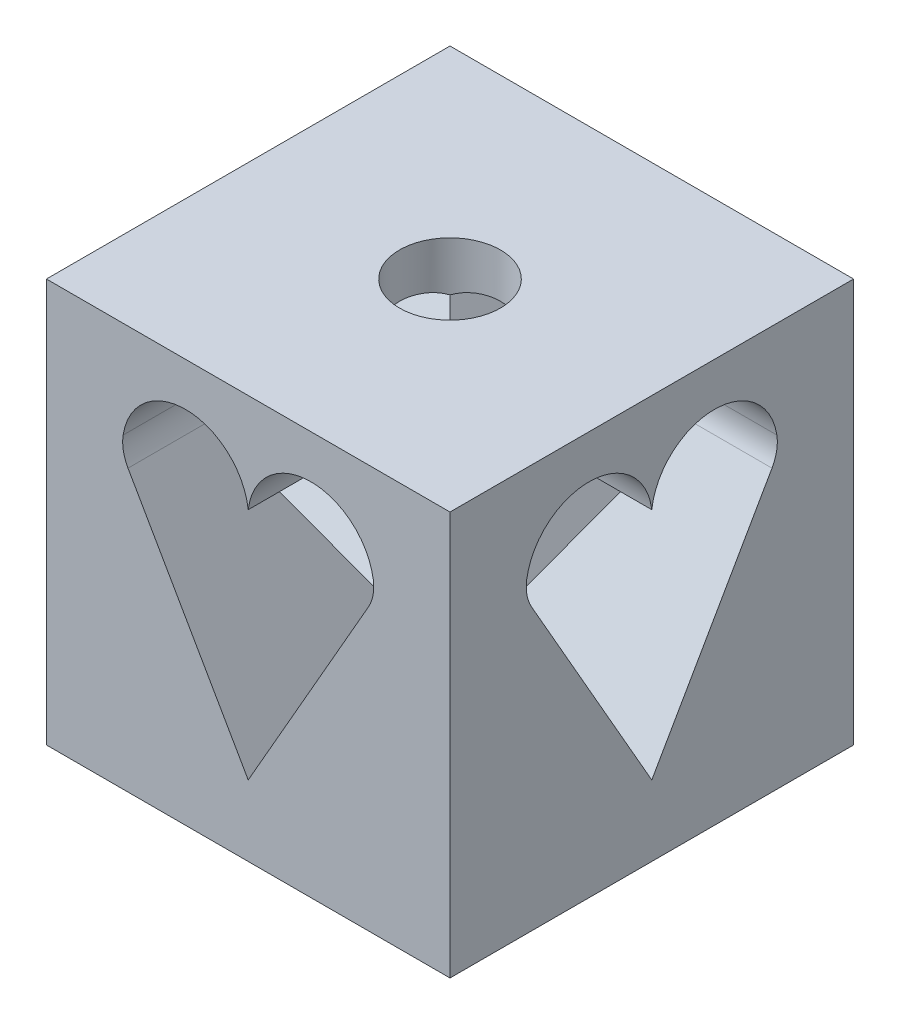
SolidWorks part; units mm, degrees
ref_plane "Front Plane" through (0, 0, 0) normal (0, 0, 1) x (1, 0, 0)
ref_plane "Top Plane" through (0, 0, 0) normal (0, 1, 0) x (1, 0, 0)
ref_plane "Right Plane" through (0, 0, 0) normal (1, 0, 0) x (0, 0, -1)
sketch "Sketch1" plane through (0, 0, 0) normal (0, 1, 0) x (1, 0, 0)
  line L1 (50, 50) -> (-50, 50)
  line L2 (50, 50) -> (50, -50)
  line L3 (50, -50) -> (-50, -50)
  line L4 (-50, 50) -> (-50, -50)
  line L5 (50, 50) -> (-50, -50) construction
  line L6 (50, -50) -> (-50, 50) construction
  point P0 (0, 0)
  dimension "D1" = 100
  dimension "D2" = 100
extrude "Boss-Extrude1" add sketch "Sketch1" along normal blind 100
ref_axis "Axis1" through (0, 105, 0) along (0, -1, 0)
sketch "Sketch2" plane through (0, 0, 50) normal (0, 0, 1) x (1, 0, 0)
  line L0 (0, 0) -> (0, 71.7452) construction
  line L1 (-50, 0) -> (50, 0) construction
  line L2 (0, 105) -> (0, -5) construction
  line L3 (0, 17.4958) -> (-29.7883, 69.5163)
  line L4 (0, 17.4958) -> (29.7883, 69.5163)
  line L5 (0, 75.4927) -> (0, 99.7792) construction
  arc A0 (-30.9918, 76.0206) -> (0, 75.4927) centre (-15.5323, 73.619) cw
  arc A1 (-29.7883, 69.5163) -> (-30.9918, 76.0206) centre (-21.1103, 74.4855) cw
  arc A2 (30.9918, 76.0206) -> (0, 75.4927) centre (15.5323, 73.619) ccw
  arc A3 (29.7883, 69.5163) -> (30.9918, 76.0206) centre (21.1103, 74.4855) ccw
  dimension "D1" = 10
  dimension "D2" = 15.6449
  dimension "D8" = 31.0646
  dimension "D3" = 59.9456
  dimension "D4" = 17.4958
  dimension "D5" = 24.2865
  dimension "D6" = 71.7452
  dimension "D7" = 29.797
extrude "Cut-Extrude1" cut sketch "Sketch2" against normal blind 50
pattern_circular "CirPattern2" count 4 over 360 about axis through (0, 105, 0) along (0, -1, 0) of "Cut-Extrude1"
sketch "Sketch3" plane through (0, 100, 0) normal (0, 1, 0) x (1, 0, 0)
  circle A0 centre (0, 0) radius 12.5
  dimension "D1" = 25
extrude "Cut-Extrude2" cut sketch "Sketch3" against normal blind 50
equation "\"D2@Sketch1\"=\"D1@Sketch1\""
equation "\"D1@Boss-Extrude1\"=\"D1@Sketch1\""
